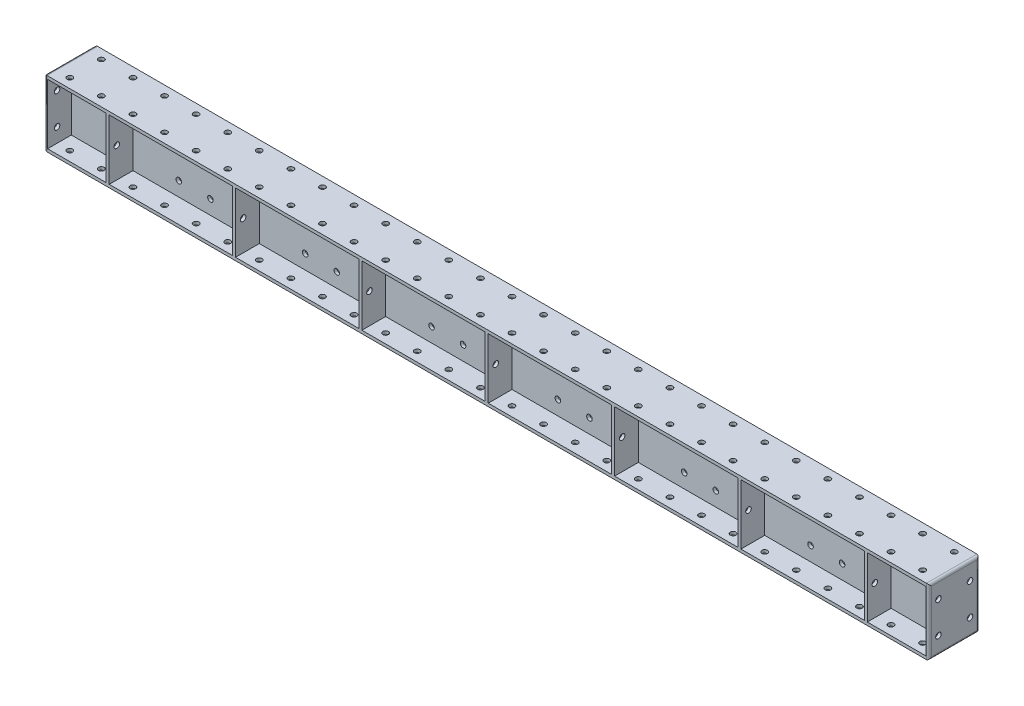
SolidWorks part; units mm, degrees
ref_plane "前视基准面" through (0, 0, 0) normal (0, 0, 1) x (1, 0, 0)
ref_plane "上视基准面" through (0, 0, 0) normal (0, 1, 0) x (1, 0, 0)
ref_plane "右视基准面" through (0, 0, 0) normal (1, 0, 0) x (0, 0, -1)
sketch "草图1" plane through (0, 0, 0) normal (0, 0, 1) x (1, 0, 0)
  line L1 (0, 0) -> (3500, 0)
  line L2 (0, 0) -> (0, 262)
  line L3 (0, 262) -> (3500, 262)
  line L4 (3500, 0) -> (3500, 262)
  dimension "D1" = 3500
  dimension "D2" = 262
extrude "拉伸1" add sketch "草图1" along normal blind 200
sketch "草图5" plane through (0, 0, 200) normal (0, 0, 1) x (1, 0, 0)
  line L0 (3500, 262) -> (0, 262) construction
  line L1 (12, 250) -> (244, 250)
  line L2 (12, 250) -> (12, 12)
  line L3 (12, 12) -> (244, 12)
  line L4 (244, 250) -> (244, 12)
  line L5 (0, 0) -> (3500, 0) construction
  line L6 (0, 262) -> (0, 0) construction
  line L8 (256, 250) -> (744, 250)
  line L9 (256, 250) -> (256, 12)
  line L10 (256, 12) -> (744, 12)
  line L11 (744, 250) -> (744, 12)
  line L12 (756, 250) -> (1244, 250)
  line L13 (756, 250) -> (756, 12)
  line L14 (756, 12) -> (1244, 12)
  line L15 (1244, 250) -> (1244, 12)
  line L16 (1256, 250) -> (1744, 250)
  line L17 (1256, 250) -> (1256, 12)
  line L18 (1256, 12) -> (1744, 12)
  line L19 (1744, 250) -> (1744, 12)
  line L20 (1756, 250) -> (2244, 250)
  line L21 (1756, 250) -> (1756, 12)
  line L22 (1756, 12) -> (2244, 12)
  line L23 (2244, 250) -> (2244, 12)
  line L24 (2256, 250) -> (2744, 250)
  line L25 (2256, 250) -> (2256, 12)
  line L26 (2256, 12) -> (2744, 12)
  line L27 (2744, 250) -> (2744, 12)
  line L28 (2756, 250) -> (3244, 250)
  line L29 (2756, 250) -> (2756, 12)
  line L30 (2756, 12) -> (3244, 12)
  line L31 (3244, 250) -> (3244, 12)
  line L32 (3256, 250) -> (3488, 250)
  line L33 (3256, 250) -> (3256, 12)
  line L34 (3256, 12) -> (3488, 12)
  line L35 (3488, 250) -> (3488, 12)
  dimension "D1" = 12
  dimension "D2" = 12
  dimension "D3" = 12
  dimension "D4" = 232
  dimension "D5" = 12
  dimension "D6" = 488
  dimension "D7" = 488
  dimension "D8" = 12
  dimension "D9" = 488
  dimension "D10" = 12
  dimension "D11" = 488
  dimension "D12" = 12
  dimension "D13" = 488
  dimension "D14" = 12
  dimension "D15" = 488
  dimension "D16" = 12
  dimension "D17" = 232
  dimension "D18" = 12
extrude "拉伸10" cut sketch "草图5" against normal through all
sketch "草图7" plane through (0, 0, 0) normal (0, -1, 0) x (1, 0, 0)
  line L0 (0, 100) -> (3607.9066, 100) construction
  line L1 (0, 200) -> (0, 0) construction
  line L2 (3500, 200) -> (3500, 0) construction
  line L3 (0, 106) -> (3500, 106)
  line L4 (0, 106) -> (0, 94)
  line L5 (0, 94) -> (3500, 94)
  line L6 (3500, 106) -> (3500, 94)
  dimension "D1" = 6
  dimension "D2" = 6
extrude "拉伸13" add sketch "草图7" against normal blind 260
sketch "草图8" plane through (0, 0, 0) normal (0, -1, 0) x (1, 0, 0)
  line L0 (0, 0) -> (3500, 0) construction
  line L1 (0, 200) -> (0, 0) construction
  circle A0 centre (62.5, 37.5) radius 11
  dimension "D1" = 37.5
  dimension "D3" = 22
  dimension "D2" = 62.5
extrude "拉伸14" cut sketch "草图8" against normal through all
pattern_linear "阵列(线性)3" count 28 spacing 125 along (1, 0, 0) count 2 spacing 125 along (0, 0, 1) of "拉伸14"
sketch "草图10" plane through (0, 0, 0) normal (-1, 0, 0) x (0, 0, 1)
  line L0 (200, 0) -> (0, 0) construction
  line L1 (0, 262) -> (0, 0) construction
  circle A0 centre (37.5, 68.5) radius 11
  dimension "D1" = 68.5
  dimension "D3" = 22
  dimension "D2" = 37.5
extrude "拉伸16" cut sketch "草图10" against normal blind 20
pattern_linear "阵列(线性)5" count 2 spacing 125 along (0, 0, 1) count 2 spacing 125 along (0, 1, 0) of "拉伸16"
sketch "草图11" plane through (3500, 0, 0) normal (1, 0, 0) x (0, 0, -1)
  line L0 (-200, 0) -> (0, 0) construction
  line L1 (-200, 0) -> (-200, 262) construction
  circle A0 centre (-162.5, 68.5) radius 11
  dimension "D1" = 68.5
  dimension "D3" = 22
  dimension "D2" = 37.5
extrude "拉伸17" cut sketch "草图11" against normal blind 20
pattern_linear "阵列(线性)6" count 2 spacing 125 along (0, 0, -1) count 2 spacing 125 along (0, 1, 0) of "拉伸17"
sketch "草图12" plane through (3256, 0, 0) normal (1, 0, 0) x (0, 0, -1)
  line L0 (-200, 250) -> (-200, 12) construction
  line L1 (-106, 12) -> (-200, 12) construction
  circle A0 centre (-170.1213, 131) radius 11
  dimension "D1" = 29.8787
  dimension "D3" = 22
  dimension "D2" = 119
extrude "拉伸18" cut sketch "草图12" against normal blind 3020
pattern_linear "阵列(线性)8" count 2 spacing 140.2427 along (0, 0, -1) of "拉伸18"
fillet "圆角1" radius 10 4 edges at (0, 0, 100) (0, 131, 0) (0, 131, 200) (0, 262, 100)
fillet "圆角2" radius 10 4 edges at (3500, 262, 100) (3500, 131, 0) (3500, 0, 100) (3500, 131, 200)
sketch "草图13" plane through (0, 0, 106) normal (0, 0, 1) x (1, 0, 0)
  line L0 (500, -750) -> (500, 49250) construction
  line L2 (256, 250) -> (744, 250) construction
  line L4 (-744, 131) -> (49256, 131) construction
  line L6 (256, 250) -> (256, 12) construction
  circle A0 centre (437.5, 68.5) radius 11
  point P5 (500, 250)
  point P10 (256, 131)
  dimension "D1" = 62.5
  dimension "D3" = 22
  dimension "D2" = 62.5
extrude "拉伸19" cut sketch "草图13" against normal through all
pattern_linear "阵列(线性)9" count 2 spacing 125 along (1, 0, 0) count 2 spacing 125 along (0, 1, 0) of "拉伸19"
pattern_linear "阵列(线性)10" count 6 spacing 500 along (1, 0, 0) of "拉伸19", "阵列(线性)9"
